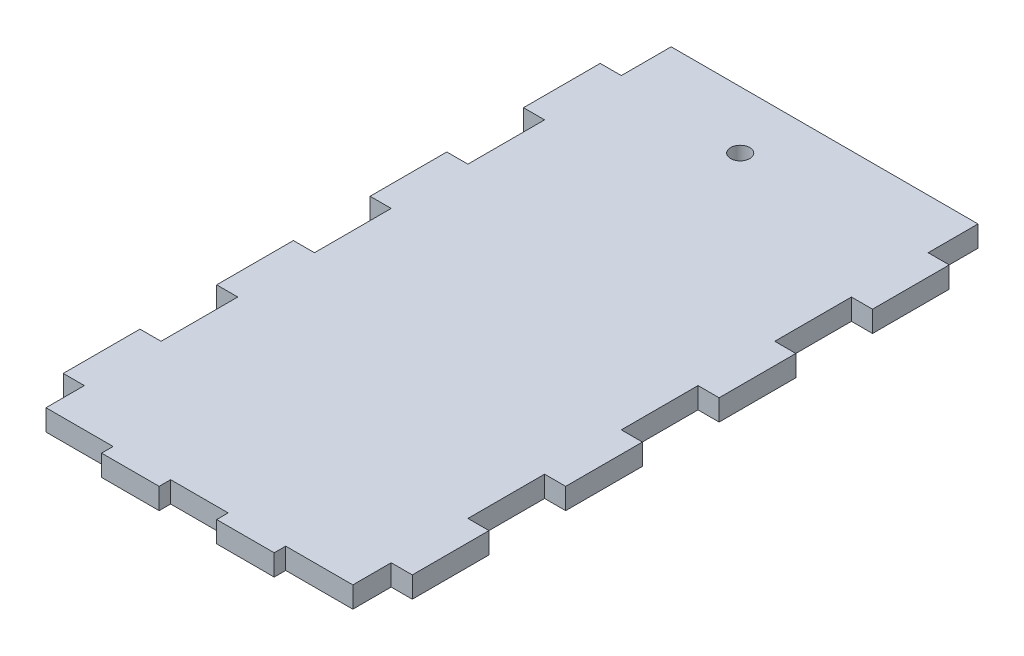
SolidWorks part; units mm, degrees
ref_plane "Alzado" through (0, 0, 0) normal (0, 0, 1) x (1, 0, 0)
ref_plane "Planta" through (0, 0, 0) normal (0, 1, 0) x (1, 0, 0)
ref_plane "Vista lateral" through (0, 0, 0) normal (1, 0, 0) x (0, 0, -1)
sketch "Croquis1" plane through (0, 0, 0) normal (0, 1, 0) x (1, 0, 0)
  line L0 (23, 0) -> (38, 0)
  line L1 (91, 13) -> (91, 33)
  line L2 (85.5, 166) -> (5.5, 166)
  line L3 (0, 153) -> (0, 93)
  line L5 (5.5, 73) -> (5.5, 93)
  line L6 (5.5, 93) -> (0, 93)
  line L7 (0, 93) -> (0, 113)
  line L8 (0, 113) -> (5.5, 113)
  line L9 (5.5, 113) -> (5.5, 133)
  line L10 (5.5, 133) -> (0, 133)
  line L11 (0, 133) -> (0, 153)
  line L12 (0, 153) -> (5.5, 153)
  line L13 (0, 13) -> (5.5, 13)
  line L14 (5.5, 33) -> (0, 33)
  line L15 (5.5, 53) -> (5.5, 33)
  line L16 (0, 53) -> (5.5, 53)
  line L17 (5.5, 73) -> (0, 73)
  line L18 (5.5, 153) -> (5.5, 166)
  line L19 (5.5, 13) -> (5.5, 3)
  line L20 (0, 33) -> (0, 13)
  line L21 (53, 3) -> (38, 3)
  line L22 (38, 3) -> (38, 0)
  line L23 (38, 0) -> (23, 0)
  line L24 (23, 0) -> (23, 3)
  line L25 (23, 3) -> (5.5, 3)
  line L26 (68, 3) -> (85.5, 3)
  line L27 (68, 0) -> (68, 3)
  line L28 (53, 3) -> (53, 0)
  line L29 (85.5, 13) -> (85.5, 3)
  line L30 (85.5, 153) -> (85.5, 166)
  line L31 (85.5, 73) -> (91, 73)
  line L32 (91, 53) -> (85.5, 53)
  line L33 (85.5, 53) -> (85.5, 33)
  line L34 (85.5, 33) -> (91, 33)
  line L35 (91, 13) -> (85.5, 13)
  line L36 (91, 153) -> (85.5, 153)
  line L37 (85.5, 133) -> (91, 133)
  line L38 (85.5, 113) -> (85.5, 133)
  line L39 (91, 113) -> (85.5, 113)
  line L40 (85.5, 93) -> (91, 93)
  line L41 (85.5, 73) -> (85.5, 93)
  line L42 (91, 133) -> (91, 153)
  line L43 (53, 0) -> (68, 0)
  line L44 (91, 53) -> (91, 73)
  line L45 (91, 93) -> (91, 113)
  line L46 (0, 73) -> (0, 53)
  circle A0 centre (38.5, 151) radius 2.5
  dimension "D4" = 5
  dimension "D5" = 20
  dimension "D6" = 20
  dimension "D7" = 20
  dimension "D10" = 15
extrude "Saliente-Extruir1" add sketch "Croquis1" along normal blind 5.5 contours L17 L46 L16 L15 L14 L20 L13 L19 L25 L24 L0 L22 L21 L28 L43 L27 L26 L29 L35 L1 L34 L33 L32 L44 L31 L41 L40 L45 L39 L38 L37 L42 L36 L30 L2 L18 L12 L3 L10 L9 L8 L6 L5 A0 region at (45.5098, 0, -83.7784)
